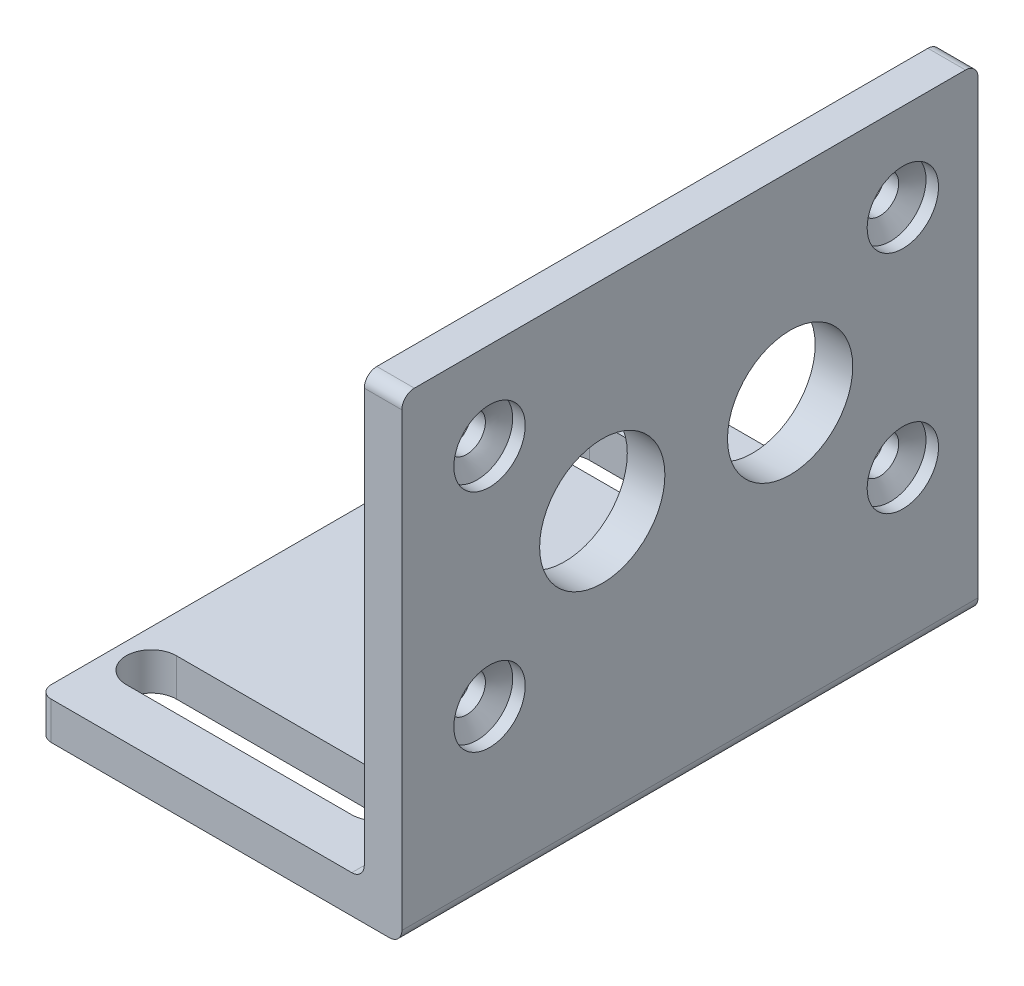
SolidWorks part; units mm, degrees
material "Aleación 1060"
ref_plane "Alzado" through (0, 0, 0) normal (0, 0, 1) x (1, 0, 0)
ref_plane "Planta" through (0, 0, 0) normal (0, 1, 0) x (1, 0, 0)
ref_plane "Vista lateral" through (0, 0, 0) normal (1, 0, 0) x (0, 0, -1)
sketch "Croquis1" plane through (0, 0, 0) normal (0, 0, 1) x (1, 0, 0)
  line L0 (-36.9164, 3.6741) -> (-36.9164, -33.3259)
  line L1 (-37.9164, -34.3259) -> (-65.9164, -34.3259)
  line L2 (-65.9164, -34.3259) -> (-65.9164, -31.3259)
  line L3 (-65.9164, -31.3259) -> (-40.9164, -31.3259)
  line L4 (-39.9164, -30.3259) -> (-39.9164, 3.6741)
  line L5 (-39.9164, 3.6741) -> (-36.9164, 3.6741)
  arc A0 (-40.9164, -31.3259) -> (-39.9164, -30.3259) centre (-40.9164, -30.3259) ccw
  arc A1 (-36.9164, -33.3259) -> (-37.9164, -34.3259) centre (-37.9164, -33.3259) cw
  point P10 (-36.9164, -34.3259)
  dimension "D5" = 1
  dimension "D1" = 3
  dimension "D2" = 38
  dimension "D3" = 29
  dimension "D4" = 3
extrude "Saliente-Extruir1" add sketch "Croquis1" along normal blind 46
fillet "Redondeo1" radius 1 4 edges at (-38.4164, 3.6741, 0) (-65.9164, -32.8259, 0) (-65.9164, -32.8259, 46) (-38.4164, 3.6741, 46)
sketch "Croquis2" plane through (-36.9164, 0, 0) normal (-1, 0, 0) x (0, 0, 1)
  line L0 (1.9889, -7.7167) -> (5.3328, -7.7167) construction
  line L3 (0, 2.6741) -> (0, -30.3259) construction
  line L7 (45, 3.6741) -> (1, 3.6741) construction
  line L9 (1.9889, -7.7167) -> (1.9889, -13.0494) construction
  circle A0 centre (6, -3.3259) radius 2.85
  circle A1 centre (39, -3.3259) radius 2.85
  circle A2 centre (6, -21.3259) radius 2.85
  circle A3 centre (39, -21.3259) radius 2.85
  circle A4 centre (15, -12.3259) radius 5
  circle A5 centre (30, -12.3259) radius 5
  dimension "D1" = 5.7
  dimension "D10" = 10
  dimension "D7" = 10
  dimension "D2" = 33
  dimension "D3" = 18
  dimension "D4" = 33
  dimension "D5" = 9
  dimension "D6" = 9
  dimension "D8" = 18
  dimension "D9" = 9
  dimension "D11" = 7
  dimension "D12" = 6
  dimension "D13" = 9
extrude "Cortar-Extruir1" cut sketch "Croquis2" along normal blind 1
sketch "Croquis3" plane through (0, -31.3259, 0) normal (0, 1, 0) x (1, 0, 0)
  line L0 (-62.9164, -42) -> (-44.9164, -42)
  line L1 (-62.9164, -38) -> (-44.9164, -38)
  line L3 (-40.9164, -46) -> (-64.9164, -46) construction
  line L4 (-73.4874, -23.5) -> (-32.2623, -23.5) construction
  line L5 (-62.9164, -9) -> (-44.9164, -9)
  line L6 (-62.9164, -5) -> (-44.9164, -5)
  arc A0 (-62.9164, -42) -> (-62.9164, -38) centre (-62.9164, -40) cw
  arc A1 (-44.9164, -38) -> (-44.9164, -42) centre (-44.9164, -40) cw
  arc A2 (-44.9164, -9) -> (-44.9164, -5) centre (-44.9164, -7) ccw
  arc A3 (-62.9164, -5) -> (-62.9164, -9) centre (-62.9164, -7) ccw
  point P6 (-53.9164, -42)
  dimension "D2" = 2
  dimension "D1" = 18
  dimension "D3" = 4
  dimension "D4" = 16.5
  dimension "D5" = 13
extrude "Cortar-Extruir2" cut sketch "Croquis3" against normal through all
ref_plane "Plano1" through (-38.7464, 0, 0) normal (1, 0, 0) x (0, 0, -1)
sketch "Croquis6" plane through (-36.9164, 0, 0) normal (1, 0, 0) x (0, 0, -1)
  circle A0 centre (-30, -12.3259) radius 5
  circle A1 centre (-15, -12.3259) radius 5
  dimension "D1" = 10
extrude "Cortar-Extruir3" cut sketch "Croquis6" against normal through all
sketch "Croquis7" plane through (-38.7464, 0, 0) normal (1, 0, 0) x (0, 0, -1)
  circle A0 centre (-39, -3.3259) radius 1.5
  circle A1 centre (-39, -21.3259) radius 1.5
  circle A2 centre (-6, -21.3259) radius 1.5
  circle A3 centre (-6, -3.3259) radius 1.5
  dimension "D1" = 3
loft "Cortar-Recubrir1" cut section edge at (-37.9164, -3.3259, 41.85) section "Croquis7" start constraint default connector at (-37.9164, -6.0715, 38.2359) connector at (-38.7464, -4.801, 39.2718)
loft "Cortar-Recubrir2" cut section edge at (-37.9164, -21.3259, 41.85) section "Croquis7<3>" connector at (-37.9164, -24.1759, 38.9964) connector at (-38.7464, -22.8259, 39.0033)
sketch "Croquis7<3>" plane through (-38.7464, 0, 0) normal (1, 0, 0) x (0, 0, -1) same geometry as "Croquis7"
loft "Cortar-Recubrir3" cut section edge at (-37.9164, -21.3259, 8.85) section "Croquis7<4>" connector at (-37.9164, -24.0509, 6.8346) connector at (-38.7464, -22.6435, 6.7168)
sketch "Croquis7<4>" plane through (-38.7464, 0, 0) normal (1, 0, 0) x (0, 0, -1) same geometry as "Croquis7"
loft "Cortar-Recubrir4" cut section edge at (-37.9164, -3.3259, 8.85) section "Croquis7<5>" connector at (-37.9164, -6.0199, 6.9299) connector at (-38.7464, -4.643, 6.7177)
sketch "Croquis7<5>" plane through (-38.7464, 0, 0) normal (1, 0, 0) x (0, 0, -1) same geometry as "Croquis7"
extrude "Cortar-Extruir4" cut sketch "Croquis7<6>" against normal through all
sketch "Croquis7<6>" plane through (-38.7464, 0, 0) normal (1, 0, 0) x (0, 0, -1) same geometry as "Croquis7"
